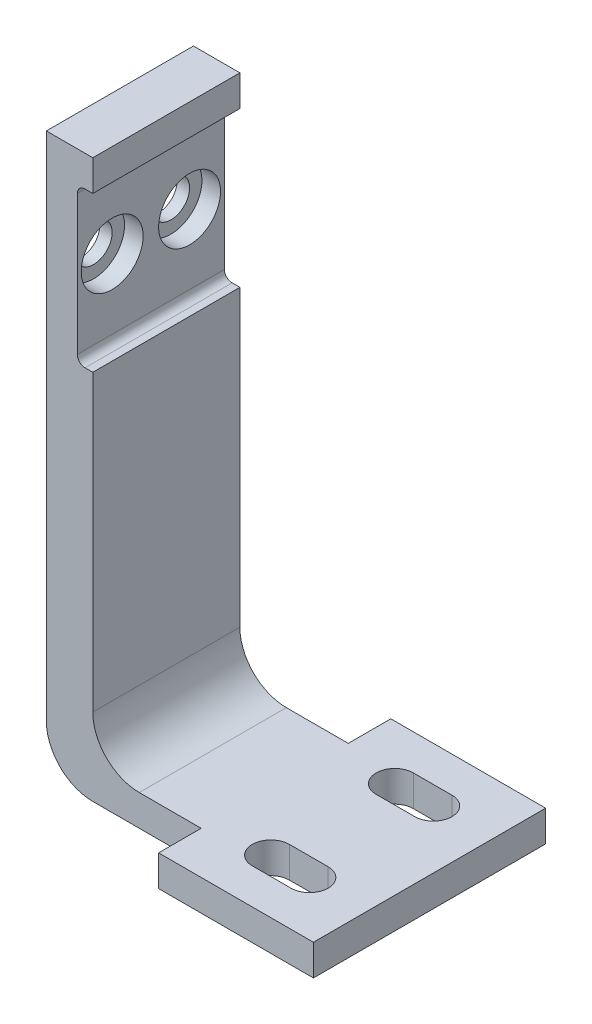
SolidWorks part; units mm, degrees
material "6061-T6 (SS)"
ref_plane "Front Plane" through (0, 0, 0) normal (0, 0, 1) x (1, 0, 0)
ref_plane "Top Plane" through (0, 0, 0) normal (0, 1, 0) x (1, 0, 0)
ref_plane "Right Plane" through (0, 0, 0) normal (1, 0, 0) x (0, 0, -1)
sketch "Sketch1" plane through (0, 0, 0) normal (0, 0, 1) x (1, 0, 0)
  line L0 (-15.4886, 20.9) -> (-17.5374, 20.9) construction
  line L9 (-17.5374, 15.9) -> (-17.5374, 25.9)
  line L10 (-19.5374, 0) -> (-19.5374, 27.9)
  line L11 (-19.5374, 27.9) -> (-16.5374, 27.9)
  line L12 (-16.5374, 27.9) -> (-16.5374, 25.9)
  line L17 (-15.4274, -6.11) -> (0.4626, -6.11)
  line L18 (0.4626, -6.11) -> (0.4626, -8.11)
  line L19 (0.4626, -8.11) -> (-11.4274, -8.11)
  line L20 (-17.5374, 25.9) -> (-16.5374, 25.9)
  line L21 (-17.5374, 15.9) -> (-16.5374, 15.9)
  line L22 (-16.5374, 15.9) -> (-16.5374, 12.9)
  line L23 (-19.5374, 0) -> (-19.5374, -8.11)
  line L24 (-19.5374, -8.11) -> (-11.4274, -8.11)
  line L25 (-16.5374, 12.9) -> (-16.5374, -6.11)
  line L26 (-16.5374, -6.11) -> (-15.4274, -6.11)
  line L29 (-15.4274, -6.11) -> (-13.0144, -6.11) construction
  point P15 (-17.5374, 20.9)
  point P21 (-12.4274, 0)
  dimension "D3" = 36.01
  dimension "D4" = 3
  dimension "D2" = 3
  dimension "D5" = 20
  dimension "D6" = 10
  dimension "D7" = 2
  dimension "D8" = 1
  dimension "D10" = 2
extrude "Boss-Extrude1" add sketch "Sketch1" along normal mid plane 9.5
sketch "Sketch2" plane through (-17.5374, 0, 0) normal (1, 0, 0) x (0, 0, -1)
  line L0 (-4.75, 20.9) -> (4.75, 20.9) construction
  line L1 (-4.75, 15.9) -> (-4.75, 25.9) construction
  line L2 (4.75, 15.9) -> (4.75, 25.9) construction
  point P8 (-2.5, 20.9)
  point P9 (0, 20.9)
  point P11 (2.5, 20.9)
  dimension "D2" = 2.5
  dimension "D1" = 2.5
hole_wizard "M2 Clearance Hole1" positions "3DSketch1" profile "Sketch3" hole size "M2" standard "ANSI Metric" end condition through all
sketch3d "3DSketch1"
  point P0 (-17.5374, 20.9, 2.5)
  point P3 (-17.5374, 20.9, -2.5)
sketch "Sketch3" plane through (-17.5374, 20.9, 2.5) normal (0, 1, 0) x (0, 0, -1)
  line L0 (0, 0) -> (0, 2)
  line L1 (0, 2) -> (1.2, 2)
  line L2 (1.2, 2) -> (1.2, 0)
  line L5 (1.2, 0) -> (0, 0)
  line L11 (0, -6.35) -> (0, 107.95) construction
  dimension "Thru Hole Dia." = 2.4
  dimension "Thru Hole Depth" = 2
sketch "Sketch4" plane through (-17.5374, 0, 0) normal (1, 0, 0) x (0, 0, -1)
  circle A0 centre (-2.5, 20.9) radius 2
  circle A1 centre (2.5, 20.9) radius 2
  dimension "D1" = 4
  dimension "D2" = 4
extrude "Cut-Extrude1" cut sketch "Sketch4" against normal blind 1.2
sketch "Sketch5" plane through (0, -8.11, 0) normal (0, -1, 0) x (1, 0, 0)
  line L0 (0.4626, -7.5) -> (0.4626, 7.5)
  line L1 (0.4626, 4.75) -> (0.4626, -4.75) construction
  line L2 (0.4626, 7.5) -> (-9.5374, 7.5)
  line L3 (-9.5374, 7.5) -> (-9.5374, -7.5)
  line L4 (-9.5374, -7.5) -> (0.4626, -7.5)
  point P3 (0.4626, 0)
  dimension "D1" = 10
  dimension "D2" = 15
extrude "Boss-Extrude2" add sketch "Sketch5" against normal blind 2
sketch "Sketch6" plane through (0, -6.11, 0) normal (0, 1, 0) x (1, 0, 0)
  line L0 (0.4626, 0) -> (-9.5374, 0) construction
  line L1 (0.4626, 7.5) -> (0.4626, -7.5) construction
  line L2 (-3.2874, -4) -> (-5.7874, -4) construction
  line L3 (-4.5374, -7.5) -> (-4.5374, 7.5) construction
  line L4 (0.4626, -7.5) -> (-9.5374, -7.5) construction
  line L5 (-9.5374, 7.5) -> (0.4626, 7.5) construction
  line L6 (-3.2874, -5.2) -> (-5.7874, -5.2)
  line L7 (-3.2874, -2.8) -> (-5.7874, -2.8)
  line L8 (-3.2874, 4) -> (-5.7874, 4) construction
  line L9 (-3.2874, 5.2) -> (-5.7874, 5.2)
  line L10 (-3.2874, 2.8) -> (-5.7874, 2.8)
  arc A0 (-3.2874, -5.2) -> (-3.2874, -2.8) centre (-3.2874, -4) ccw
  arc A1 (-5.7874, -2.8) -> (-5.7874, -5.2) centre (-5.7874, -4) ccw
  arc A2 (-3.2874, 5.2) -> (-3.2874, 2.8) centre (-3.2874, 4) cw
  arc A3 (-5.7874, 2.8) -> (-5.7874, 5.2) centre (-5.7874, 4) cw
  point P12 (-4.5374, -4)
  point P13 (-4.5374, 0)
  point P14 (-4.5374, 4)
  point P15 (-4.5374, -4)
  point P23 (-4.5374, 4)
  dimension "D3" = 1.2
  dimension "D1" = 4
  dimension "D2" = 2.5
extrude "Cut-Extrude2" cut sketch "Sketch6" against normal up to surface (2 mm away) up to face at (-9.5374, -8.11, 0)
fillet "Fillet1" radius 3 2 edges at (-16.5374, -6.11, 0) (-19.5374, -8.11, 0)
fillet "Fillet2" radius 0.5 2 edges at (-17.5374, 15.9, 0) (-17.5374, 25.9, 0)
